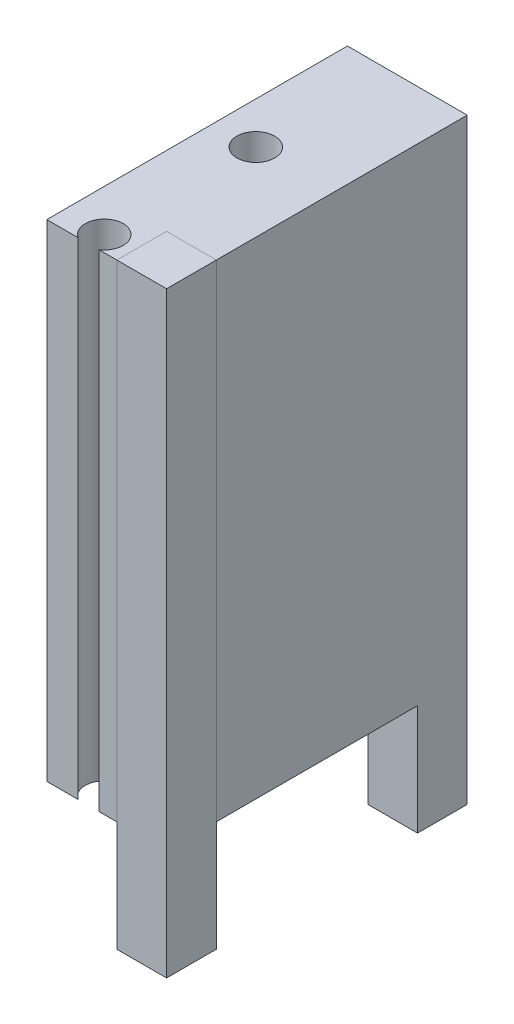
SolidWorks part; units mm, degrees
ref_plane "Front Plane" through (0, 0, 0) normal (0, 0, 1) x (1, 0, 0)
ref_plane "Top Plane" through (0, 0, 0) normal (0, 1, 0) x (1, 0, 0)
ref_plane "Right Plane" through (0, 0, 0) normal (1, 0, 0) x (0, 0, -1)
sketch "Sketch2" plane through (0, 0, 48.9685) normal (0, 0, -1) x (-1, 0, 0)
  line L0 (4.4, 21.755) -> (4.4, 31.755) construction
  line L1 (4.4, 47.555) -> (4.4, 57.555) construction
  line L2 (0, 35.655) -> (-3.5, 35.655) construction
  line L3 (0, 35.655) -> (4.4, 35.655) construction
  line L4 (-3.5, 27.655) -> (0, 27.655) construction
  line L5 (4.4, 27.655) -> (0, 27.655) construction
  line L6 (-3.5, 43.655) -> (0, 43.655) construction
  line L7 (4.4, 43.655) -> (0, 43.655) construction
  line L8 (0, 51.655) -> (-3.5, 51.655) construction
  line L9 (0, 51.655) -> (4.4, 51.655) construction
  line L10 (-3.6, 51.555) -> (-3.6, 43.755) construction
  line L11 (-3.6, 27.755) -> (-3.6, 35.555) construction
  line L12 (4.4, 21.755) -> (4.4, 27.655)
  line L13 (4.4, 51.655) -> (4.4, 57.555)
  line L14 (0, 35.655) -> (-3.6, 35.655)
  line L15 (0, 35.655) -> (4.4, 35.655)
  line L16 (-3.6, 27.655) -> (0, 27.655)
  line L17 (4.4, 27.655) -> (0, 27.655)
  line L18 (-3.6, 43.655) -> (0, 43.655)
  line L19 (4.4, 43.655) -> (0, 43.655)
  line L20 (0, 51.655) -> (-3.6, 51.655)
  line L21 (0, 51.655) -> (4.4, 51.655)
  line L22 (-3.6, 51.655) -> (-3.6, 43.655)
  line L23 (-3.6, 27.655) -> (-3.6, 35.655)
  line L24 (4.4, 21.755) -> (-8.25, 21.755)
  line L25 (-8.25, 10) -> (-8.25, 21.655) construction
  line L26 (-8.25, 21.755) -> (-8.25, 57.555)
  line L27 (-8.25, 57.555) -> (4.4, 57.555)
  line L28 (4.4, 43.655) -> (4.4, 35.655)
extrude "Boss-Extrude1" add sketch "Sketch2" along normal up to surface and the other way up to surface rebuild error yes
sketch "Sketch4" plane through (0, 73.037, 0) normal (0, -1, 0) x (1, 0, 0)
  line L0 (3, 12.6052) -> (8.25, 12.6052) construction
  line L1 (-4.4, 7.3552) -> (8.25, 7.3552) construction
  line L2 (3, 7.3552) -> (3, 12.6052) construction
  line L3 (-4.4, 39.1052) -> (8.25, 39.1052) construction
  line L4 (8.25, 7.3552) -> (8.25, 39.1052) construction
  line L5 (8.25, 33.8552) -> (3, 33.8552) construction
  line L6 (3, 33.8552) -> (3, 39.1052) construction
  line L7 (3, 12.6052) -> (8.25, 12.6052)
  line L8 (3, 7.3552) -> (8.25, 7.3552)
  line L9 (3, 7.3552) -> (3, 12.6052)
  line L10 (3, 39.1052) -> (8.25, 39.1052)
  line L11 (8.25, 7.3552) -> (8.25, 39.1052)
  line L12 (8.25, 33.8552) -> (3, 33.8552)
  line L13 (3, 33.8552) -> (3, 39.1052)
extrude "Boss-Extrude2" add sketch "Sketch4" along normal up to surface (63.037 mm away) contours L13 L12 L11 | L9 L7 region at (5.625, 73.037, 36.4802) region at (5.625, 73.037, 9.9802)
sketch "Sketch6" plane through (0, 73.037, 0) normal (0, -1, 0) x (1, 0, 0)
  line L8 (3, 7.3552) -> (3, 12.6052)
  line L9 (3, 12.6052) -> (8.25, 12.6052)
  line L10 (8.25, 12.6052) -> (8.25, 33.8552)
  line L11 (8.25, 33.8552) -> (3, 33.8552)
  line L12 (3, 33.8552) -> (3, 39.1052)
  line L13 (3, 39.1052) -> (-4.4, 39.1052)
  line L14 (-4.4, 39.1052) -> (-4.4, 7.3552)
  line L15 (-4.4, 7.3552) -> (3, 7.3552)
  line L16 (3, 7.3552) -> (3, 12.6052)
  line L17 (3, 12.6052) -> (8.25, 12.6052)
  line L18 (8.25, 12.6052) -> (8.25, 33.8552)
  line L19 (8.25, 33.8552) -> (3, 33.8552)
  line L20 (3, 33.8552) -> (3, 39.1052)
  line L21 (3, 39.1052) -> (-4.4, 39.1052)
  line L22 (-4.4, 39.1052) -> (-4.4, 7.3552)
  line L23 (-4.4, 7.3552) -> (3, 7.3552)
  dimension "D1" = 0
extrude "Boss-Extrude3" add sketch "Sketch6" along normal up to surface (51.382 mm away)
sketch "Sketch7" plane through (0, 108.837, 0) normal (0, 1, 0) x (1, 0, 0)
  circle A0 centre (0, -21.4363) radius 1.8 construction
  circle A1 centre (0, -37.4363) radius 1.8 construction
  circle A2 centre (0, -21.4363) radius 1.8 construction
  circle A3 centre (0, -37.4363) radius 1.8 construction
  circle A4 centre (0, -37.4363) radius 2
  circle A5 centre (0, -21.4363) radius 2
  dimension "D1" = 0.2
extrude "Cut-Extrude1" cut sketch "Sketch7" against normal through all
